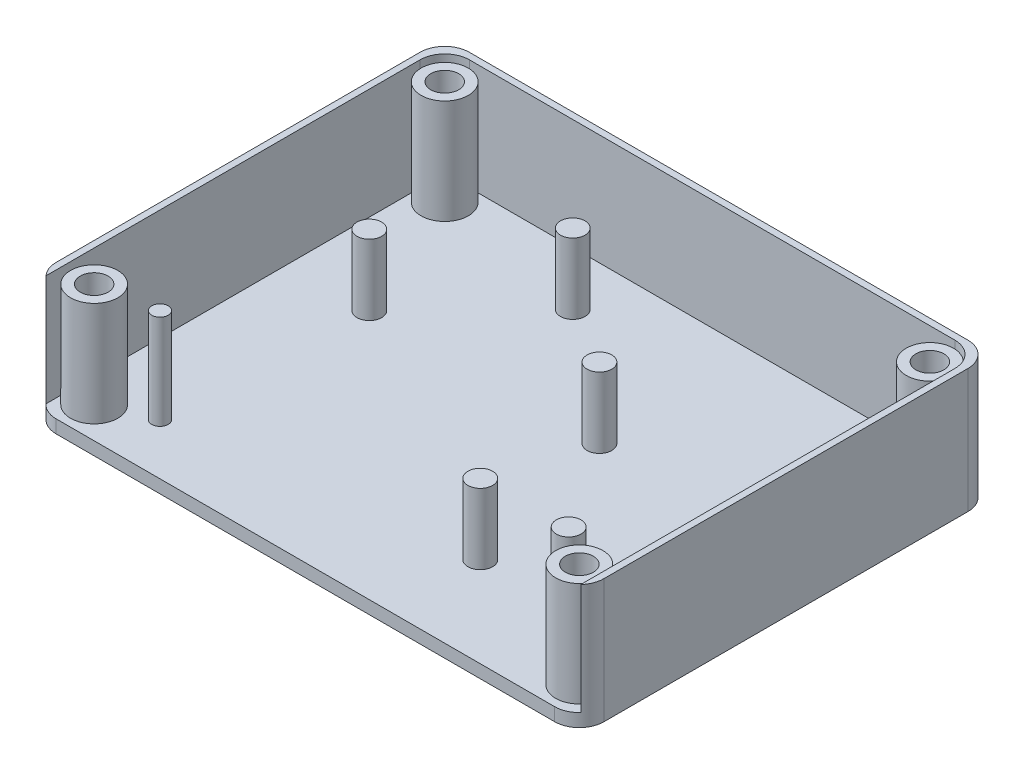
SolidWorks part; units mm, degrees
ref_plane "Front Plane" through (0, 0, 0) normal (0, 0, 1) x (1, 0, 0)
ref_plane "Top Plane" through (0, 0, 0) normal (0, 1, 0) x (1, 0, 0)
ref_plane "Right Plane" through (0, 0, 0) normal (1, 0, 0) x (0, 0, -1)
sketch "Sketch1" plane through (0, 0, 0) normal (0, 1, 0) x (1, 0, 0)
  line L0 (-66.8583, -50.2762) -> (-65.2708, -50.2762)
  line L1 (-65.2708, -50.2762) -> (64.8554, -50.2762)
  line L2 (-66.8583, -50.2762) -> (-66.8583, 44.2663)
  line L3 (-60.8583, 50.2663) -> (60.4429, 50.2663)
  line L4 (66.4429, -50.2762) -> (66.4429, 44.2663)
  line L5 (66.4429, -50.2762) -> (64.8554, -50.2762)
  line L6 (-50.3864, 41.1329) -> (-50.3864, 5.0649)
  line L7 (-50.3483, 41.1463) -> (49.9329, 41.1463)
  line L8 (-65.2708, -50.2762) -> (-65.2708, 42.6788)
  line L9 (-59.2708, 48.6788) -> (58.8554, 48.6788)
  line L10 (64.8554, -50.2762) -> (64.8554, 42.6788)
  line L11 (-50.3483, 41.1463) -> (-50.3483, -40.1162)
  line L12 (-50.3483, -40.1162) -> (49.9329, -40.1162)
  line L13 (49.9329, 41.1463) -> (49.9329, -40.1162)
  line L14 (-50.3864, 5.0649) -> (14.3836, 5.0649)
  line L15 (14.3836, 5.0649) -> (14.3836, -33.7971)
  line L16 (14.3836, -33.7971) -> (47.4036, -33.7971)
  line L17 (47.4036, -33.7971) -> (47.4036, 41.1329)
  line L18 (47.4036, 41.1329) -> (-50.3864, 41.1329)
  circle A0 centre (-59.2383, 42.6463) radius 3.4
  circle A1 centre (-59.2383, 42.6463) radius 5.75
  circle A2 centre (58.8229, 42.6463) radius 5.75
  circle A3 centre (58.8229, 42.6463) radius 3.4
  circle A4 centre (-59.2383, -42.6562) radius 5.75
  circle A5 centre (-59.2383, -42.6562) radius 3.4
  circle A6 centre (58.8229, -42.6562) radius 5.75
  circle A7 centre (58.8229, -42.6562) radius 3.4
  circle A8 centre (-21.0872, 35.6529) radius 3
  circle A9 centre (20.4128, -28.3471) radius 3
  circle A10 centre (-45.5872, 10.6529) radius 3
  circle A11 centre (10.4128, 10.6529) radius 3
  circle A12 centre (41.4128, -27.8471) radius 3
  arc A13 (-66.8583, 44.2663) -> (-60.8583, 50.2663) centre (-60.8583, 44.2663) cw
  arc A14 (-65.2708, 42.6788) -> (-59.2708, 48.6788) centre (-59.2708, 42.6788) cw
  circle A15 centre (-48.0512, -37.8237) radius 2
  arc A16 (58.8554, 48.6788) -> (64.8554, 42.6788) centre (58.8554, 42.6788) cw
  arc A17 (60.4429, 50.2663) -> (66.4429, 44.2663) centre (60.4429, 44.2663) cw
  point P0 (0, 0)
  point P44 (-66.8583, 50.2663)
  point P53 (66.4429, 50.2663)
  dimension "D5" = 7.62
  dimension "D7" = 7.62
  dimension "D18" = 97.79
  dimension "D20" = 64.77
  dimension "D26" = 24.5
  dimension "D32" = 6
  dimension "D33" = 6
  dimension "D34" = 6
  dimension "D1" = 133.3013
  dimension "D2" = 100.5425
  dimension "D3" = 1.5875
  dimension "D4" = 1.5875
  dimension "D6" = 7.62
  dimension "D8" = 7.62
  dimension "D9" = 7.62
  dimension "D10" = 7.62
  dimension "D11" = 7.62
  dimension "D12" = 7.62
  dimension "D13" = 1.5875
  dimension "D14" = 9.12
  dimension "D15" = 16.51
  dimension "D16" = 16.51
  dimension "D17" = 81.2625
  dimension "D19" = 36.068
  dimension "D21" = 74.93
  dimension "D22" = 5.588
  dimension "D23" = 5.588
  dimension "D24" = 7.366
  dimension "D25" = 56
  dimension "D27" = 25
  dimension "D28" = 10
  dimension "D29" = 21
  dimension "D30" = 39
  dimension "D31" = 0.5
extrude "Boss-Extrude12" add sketch "Sketch1" along normal blind 3.175 contours L5 L4 A17 L3 A13 L2 L0 L1
extrude "Boss-Extrude13" add sketch "Sketch1<23>" along normal blind 30.1625 contours L10 L5 L4 L3 L2 L0 L8 L9 region at (-66.6913, 0, 3.005)
sketch "Sketch1<23>" plane through (0, 0, 0) normal (0, 1, 0) x (1, 0, 0) same geometry as "Sketch1"
extrude "Boss-Extrude15" add sketch "Sketch1<25>" along normal blind 28.575 contours A1 A0 | A2 A3 | A6 A7 | A4 A5 region at (-64.8257, 0, -42.6463) region at (53.2356, 0, -42.6463) region at (-64.8257, 0, 42.6562) region at (53.2356, 0, 42.6562)
sketch "Sketch1<25>" plane through (0, 0, 0) normal (0, 1, 0) x (1, 0, 0) same geometry as "Sketch1"
extrude "Cut-Extrude3" cut sketch "Sketch1<27>" along normal blind 28.575 contours A5 | A5 | A0 | A3 | A7 region at (-59.2383, 0, 42.6562)
sketch "Sketch1<27>" plane through (0, 0, 0) normal (0, 1, 0) x (1, 0, 0) same geometry as "Sketch1"
chamfer "Chamfer2" distance 1.45 angle 45 4 edges at (58.8229, 0, 46.0562) (58.8229, 0, -39.2463) (-59.2383, 0, 46.0562) (-59.2383, 0, -39.2463)
extrude "Boss-Extrude16" add sketch "Sketch1<28>" along normal blind 20.32 contours A12 | A9 | A8 | A10 | A11 region at (20.4128, 0, 28.3471) region at (41.4128, 0, 27.8471)
sketch "Sketch1<28>" plane through (0, 0, 0) normal (0, 1, 0) x (1, 0, 0) same geometry as "Sketch1"
extrude "Boss-Extrude17" add sketch "Sketch1<29>" along normal blind 26.1874 contours A15 region at (-48.0512, 0, 37.8237)
sketch "Sketch1<29>" plane through (0, 0, 0) normal (0, 1, 0) x (1, 0, 0) same geometry as "Sketch1"
fillet "Fillet3" radius 6 2 edges at (66.4429, 15.0812, 50.2762) (-66.8583, 15.0812, 50.2762)
